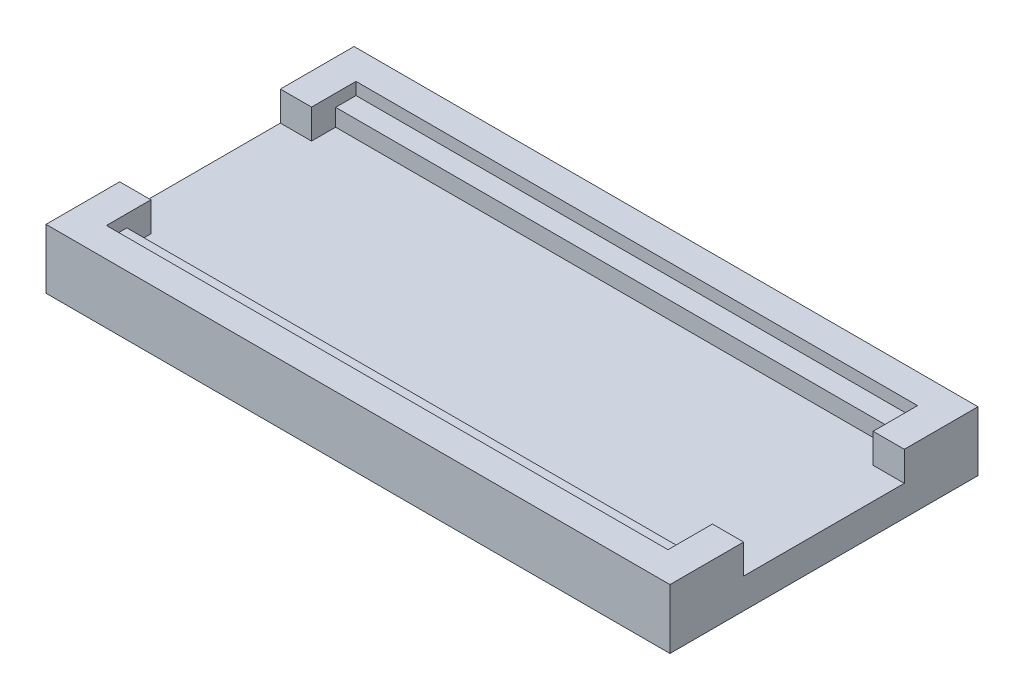
SolidWorks part; units mm, degrees
material "Delrin 2700 NC010, Low Viscosity Acetal Copolymer (SS)"
ref_plane "Front Plane" through (0, 0, 0) normal (0, 0, 1) x (1, 0, 0)
ref_plane "Top Plane" through (0, 0, 0) normal (0, 1, 0) x (1, 0, 0)
ref_plane "Right Plane" through (0, 0, 0) normal (1, 0, 0) x (0, 0, -1)
sketch "Sketch1" plane through (0, 0, 0) normal (0, 1, 0) x (1, 0, 0)
  line L1 (0, 0) -> (254, 0)
  line L2 (0, 0) -> (0, 125.4)
  line L3 (0, 125.4) -> (254, 125.4)
  line L4 (254, 0) -> (254, 125.4)
  dimension "D1" = 125.4
  dimension "D2" = 254
extrude "Boss-Extrude1" add sketch "Sketch1" along normal blind 24.3
sketch "Sketch2" plane through (0, 24.3, 0) normal (0, 1, 0) x (1, 0, 0)
  line L0 (0, 125.4) -> (0, 0) construction
  line L1 (12.7, 113.5) -> (241.3, 113.5)
  line L2 (12.7, 113.5) -> (12.7, 11.9)
  line L3 (12.7, 11.9) -> (241.3, 11.9)
  line L4 (241.3, 113.5) -> (241.3, 11.9)
  line L5 (0, 0) -> (254, 0) construction
  line L6 (254, 0) -> (254, 125.4) construction
  line L7 (254, 125.4) -> (0, 125.4) construction
  dimension "D1" = 12.7
  dimension "D2" = 11.9
  dimension "D3" = 11.9
  dimension "D4" = 12.7
extrude "Cut-Extrude1" cut sketch "Sketch2" against normal blind 5
sketch "Sketch3" plane through (0, 19.3, 0) normal (0, 1, 0) x (1, 0, 0)
  line L1 (241.3, 105.2) -> (12.7, 105.2)
  line L2 (241.3, 105.2) -> (241.3, 20.2)
  line L3 (241.3, 20.2) -> (12.7, 20.2)
  line L4 (12.7, 105.2) -> (12.7, 20.2)
  line L5 (241.3, 113.5) -> (12.7, 113.5) construction
  line L6 (12.7, 113.5) -> (12.7, 11.9) construction
  line L7 (241.3, 11.9) -> (241.3, 113.5) construction
  line L8 (12.7, 11.9) -> (241.3, 11.9) construction
  dimension "D1" = 8.3
  dimension "D3" = 8.3
extrude "Cut-Extrude2" cut sketch "Sketch3" against normal blind 7
sketch "Sketch4" plane through (0, 24.3, 0) normal (0, 1, 0) x (1, 0, 0)
  line L0 (0, 125.4) -> (0, 0) construction
  line L1 (0, 30) -> (12.7, 30)
  line L2 (0, 30) -> (0, 95.4)
  line L3 (0, 95.4) -> (12.7, 95.4)
  line L4 (12.7, 30) -> (12.7, 95.4)
  line L5 (12.7, 113.5) -> (12.7, 11.9) construction
  line L6 (0, 0) -> (254, 0) construction
  line L7 (254, 125.4) -> (0, 125.4) construction
  dimension "D1" = 30
  dimension "D2" = 30
extrude "Cut-Extrude3" cut sketch "Sketch4" against normal blind 12
sketch "Sketch5" plane through (0, 24.3, 0) normal (0, 1, 0) x (1, 0, 0)
  line L0 (254, 0) -> (254, 125.4) construction
  line L1 (254, 95.4) -> (241.3, 95.4)
  line L2 (254, 95.4) -> (254, 30)
  line L3 (254, 30) -> (241.3, 30)
  line L4 (241.3, 95.4) -> (241.3, 30)
  line L5 (241.3, 11.9) -> (241.3, 113.5) construction
  line L6 (0, 0) -> (254, 0) construction
  line L7 (254, 125.4) -> (0, 125.4) construction
  dimension "D1" = 30
  dimension "D2" = 30
extrude "Cut-Extrude4" cut sketch "Sketch5" against normal blind 12
